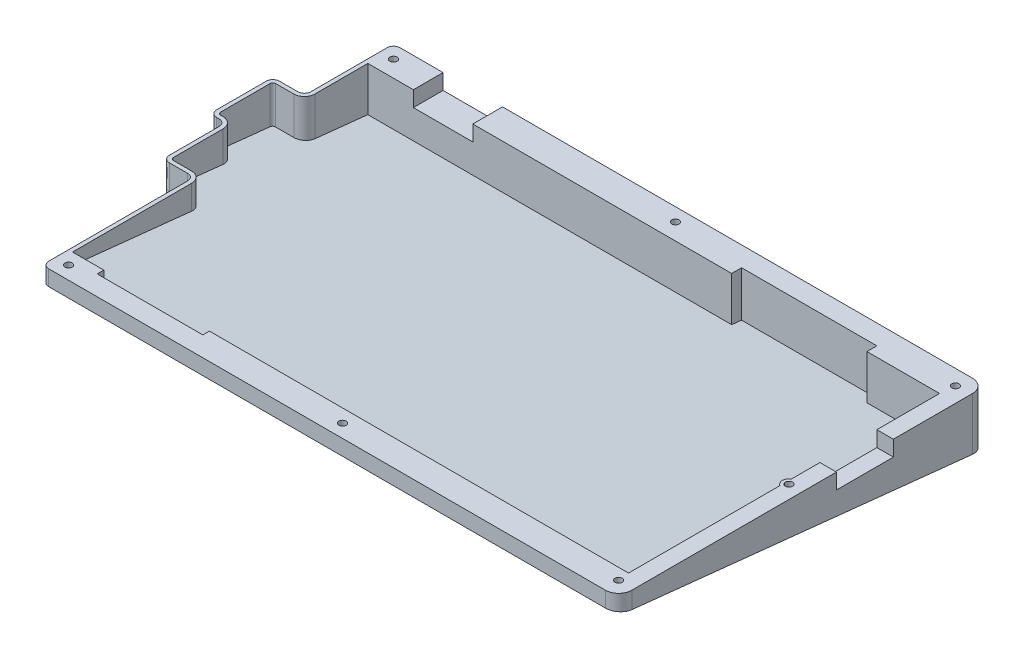
SolidWorks part; units mm, degrees
ref_plane "Front Plane" through (0, 0, 0) normal (0, 0, 1) x (1, 0, 0)
ref_plane "Top Plane" through (0, 0, 0) normal (0, 1, 0) x (1, 0, 0)
ref_plane "Right Plane" through (0, 0, 0) normal (1, 0, 0) x (0, 0, -1)
sketch "Sketch1" plane through (0, 0, 0) normal (0, 1, 0) x (1, 0, 0)
  line L0 (138.4196, 31.7518) -> (125.4196, 31.7518)
  line L1 (-35.0204, 31.7518) -> (107.4196, 31.7518)
  line L2 (140.4196, 29.7518) -> (140.4196, 6.7018)
  line L3 (-34.0204, 3.7518) -> (-34.0204, 22.7518)
  line L4 (136.4596, 27.7518) -> (136.4396, 27.7518)
  line L5 (142.4196, 4.7018) -> (147.9496, 4.7018)
  line L6 (-34.0204, 22.7518) -> (-12.0204, 22.7518)
  line L8 (149.9496, 2.7018) -> (149.9496, -12.3482)
  line L11 (147.9496, -14.3482) -> (147.1896, -14.3482)
  line L14 (145.1896, -16.3482) -> (145.1896, -31.3982)
  line L17 (143.1896, -33.3982) -> (137.6696, -33.3982)
  line L20 (135.6696, -35.3982) -> (135.6696, -77.4982)
  line L21 (-34.0204, -25.6003) -> (-34.0204, -71.4982)
  line L23 (133.6696, -79.4982) -> (-35.0204, -79.4982)
  line L28 (-39.0204, 27.7518) -> (-39.0204, 3.7518)
  line L31 (-34.0204, 3.7518) -> (-39.0204, 3.7518)
  line L32 (-34.0204, -13.4982) -> (-39.0204, -13.4982)
  line L33 (-39.0204, -75.4982) -> (-39.0204, -13.4982)
  line L34 (-34.0204, -71.4982) -> (92.9796, -71.4982)
  line L35 (92.9796, -71.4982) -> (92.9796, -73.4982)
  line L36 (92.9796, -73.4982) -> (124.9796, -73.4982)
  line L37 (124.9796, -73.4982) -> (124.9796, -71.4982)
  line L39 (134.4706, -35.3982) -> (134.4706, -71.4982)
  line L40 (134.4706, -71.4982) -> (124.9796, -71.4982)
  line L41 (137.6696, -32.1992) -> (143.1896, -32.1992)
  line L42 (-34.0204, -13.4982) -> (-34.0204, -22.1362)
  line L43 (143.9906, -31.3982) -> (143.9906, -16.3482)
  line L44 (-12.0204, 22.7518) -> (-12.0204, 25.7518)
  line L45 (147.1896, -13.1492) -> (147.9496, -13.1492)
  line L46 (148.7506, -12.3482) -> (148.7506, 2.7018)
  line L47 (-12.0204, 25.7518) -> (28.9796, 25.7518)
  line L48 (28.9796, 25.7518) -> (28.9796, 22.7518)
  line L49 (28.9796, 22.7518) -> (107.4196, 22.7518)
  line L50 (147.9496, 3.5027) -> (142.4196, 3.5027)
  line L51 (107.4196, 22.7518) -> (107.4196, 31.7518)
  line L52 (139.2206, 6.7018) -> (139.2206, 22.7518)
  line L53 (125.4196, 31.7518) -> (125.4196, 22.7518)
  line L54 (139.2206, 22.7518) -> (125.4196, 22.7518)
  arc A0 (138.4196, 31.7518) -> (140.4196, 29.7518) centre (138.4196, 29.7518) cw
  arc A1 (140.4196, 6.7018) -> (142.4196, 4.7018) centre (142.4196, 6.7018) ccw
  arc A2 (149.9496, 2.7018) -> (147.9496, 4.7018) centre (147.9496, 2.7018) ccw
  arc A3 (149.9496, -12.3482) -> (147.9496, -14.3482) centre (147.9496, -12.3482) cw
  arc A4 (147.1896, -14.3482) -> (145.1896, -16.3482) centre (147.1896, -16.3482) ccw
  arc A5 (145.1896, -31.3982) -> (143.1896, -33.3982) centre (143.1896, -31.3982) cw
  arc A6 (-35.0204, 31.7518) -> (-39.0204, 27.7518) centre (-35.0204, 27.7518) ccw
  arc A7 (-39.0204, -75.4982) -> (-35.0204, -79.4982) centre (-35.0204, -75.4982) ccw
  arc A8 (133.6696, -79.4982) -> (135.6696, -77.4982) centre (133.6696, -77.4982) ccw
  arc A9 (135.6696, -35.3982) -> (137.6696, -33.3982) centre (137.6696, -35.3982) cw
  circle A10 centre (-34.4204, 27.1518) radius 1.1
  circle A11 centre (51.0096, 27.7518) radius 1.1
  circle A12 centre (136.4396, 27.7518) radius 1.1
  circle A13 centre (-34.4204, -74.8982) radius 1.1
  circle A14 centre (48.6296, -75.4982) radius 1.1
  circle A15 centre (131.6496, -75.4982) radius 1.1
  circle A16 centre (-35.0204, -23.8682) radius 1.1
  arc A27 (-34.0204, -22.1362) -> (-34.0204, -25.6003) centre (-35.0204, -23.8682) cw
  arc A28 (139.2206, 6.7018) -> (142.4196, 3.5027) centre (142.4196, 6.7018) ccw
  arc A29 (147.9496, 3.5027) -> (148.7506, 2.7018) centre (147.9496, 2.7018) cw
  arc A30 (148.7506, -12.3482) -> (147.9496, -13.1492) centre (147.9496, -12.3482) cw
  arc A31 (147.1896, -13.1492) -> (143.9906, -16.3482) centre (147.1896, -16.3482) ccw
  arc A32 (143.9906, -31.3982) -> (143.1896, -32.1992) centre (143.1896, -31.3982) cw
  arc A33 (137.6696, -32.1992) -> (134.4706, -35.3982) centre (137.6696, -35.3982) ccw
extrude "Boss-Extrude2" add sketch "Sketch1" against normal blind 4.7 contours L41 A33 L39 L40 L37 L36 L35 L34 L21 A27 L42 L32 L33 A7 L23 A8 L20 A9 L17 A5 L14 A4 L11 A3 L8 A2 L5 A1 L2 A0 L0 L53 L54 L52 A28 L50 A29 L46 A30 L45 A31 L43 A32 A12 A13 A14 A15 | L1 A6 L28 L31 L3 L6 L44 L47 L48 L49 L51 A11 A10 region at (138.2833, 0, -29.6154) region at (31.7683, 0, -26.4895)
move or copy body "Body-Move/Copy1" bodies to move or copy 105 104 copy no rotation origin (55.4646, -2.35, 0) rotation axis (0, 0, 1) rotation angle 180
sketch "Sketch3" plane through (149.9496, 0, 0) normal (1, 0, 0) x (0, 0, -1)
  line L0 (-79.4982, 0) -> (-79.4982, -4.7) construction
  line L1 (-79.4982, 0) -> (-79.4982, -4.7)
  line L2 (31.7518, 0) -> (31.7518, -4.7) construction
  line L3 (31.7518, 0) -> (31.7518, -4.7)
  line L5 (-79.4982, -4.7) -> (31.7518, -16.3928)
  line L6 (31.7518, -16.3928) -> (31.7518, -4.7)
  line L7 (31.7518, -4.7) -> (-79.4982, -4.7)
  line M3 (-75.4982, -4.7) -> (-13.4982, -4.7)
  dimension "D1" = 6
extrude "Boss-Extrude3" add sketch "Sketch3" against normal up to surface (188.97 mm away) contours L6 L7 L5 M3 region at (149.9496, -8.5976, 5.3315) up to face at (-39.0204, -2.35, 4.8232)
sketch "Sketch4" plane through (0, -4.7, 0) normal (0, 1, 0) x (1, 0, 0)
  line L2 (145.9496, -79.4982) -> (149.9496, -79.4982)
  line L3 (149.9496, -79.4982) -> (149.9496, -75.4982)
  line L4 (-29.4904, 6.7018) -> (-29.4904, 29.7518)
  line L5 (-27.4904, 31.7518) -> (-39.0204, 31.7518)
  line L6 (-36.2604, -14.3482) -> (-37.0204, -14.3482)
  line L7 (-39.0204, -12.3482) -> (-39.0204, -79.4982)
  line L8 (-39.0204, -79.4982) -> (-22.7404, -79.4982)
  line L9 (-24.7404, -77.4982) -> (-24.7404, -35.3982)
  line L10 (-26.7404, -33.3982) -> (-32.2604, -33.3982)
  line L11 (-34.2604, -31.3982) -> (-34.2604, -16.3482)
  line L12 (-36.2604, -14.3482) -> (-37.0204, -14.3482)
  line L13 (-39.0204, -12.3482) -> (-39.0204, -79.4982)
  line L14 (-39.0204, -79.4982) -> (-22.7404, -79.4982)
  line L15 (-24.7404, -77.4982) -> (-24.7404, -35.3982)
  line L16 (-26.7404, -33.3982) -> (-32.2604, -33.3982)
  line L17 (-34.2604, -31.3982) -> (-34.2604, -16.3482)
  line L18 (-39.0204, 31.7518) -> (-39.0204, 2.7018)
  line L19 (-37.0204, 4.7018) -> (-31.4904, 4.7018)
  line L20 (-29.4904, 6.7018) -> (-29.4904, 29.7518)
  line L21 (-27.4904, 31.7518) -> (-39.0204, 31.7518)
  line L22 (-39.0204, 31.7518) -> (-39.0204, 2.7018)
  line L23 (-37.0204, 4.7018) -> (-31.4904, 4.7018)
  line L24 (145.9496, -79.4982) -> (149.9496, -79.4982)
  line L25 (149.9496, -79.4982) -> (149.9496, -75.4982)
  line L26 (149.9496, 31.7518) -> (145.9496, 31.7518)
  line L27 (149.9496, 27.7518) -> (149.9496, 31.7518)
  line L28 (149.9496, 31.7518) -> (145.9496, 31.7518)
  line L29 (149.9496, 27.7518) -> (149.9496, 31.7518)
  arc A1 (145.9496, -79.4982) -> (149.9496, -75.4982) centre (145.9496, -75.4982) ccw
  arc A2 (145.9496, -79.4982) -> (149.9496, -75.4982) centre (145.9496, -75.4982) ccw
  arc A3 (-27.4904, 31.7518) -> (-29.4904, 29.7518) centre (-27.4904, 29.7518) ccw
  arc A4 (-37.0204, 4.7018) -> (-39.0204, 2.7018) centre (-37.0204, 2.7018) ccw
  arc A5 (-39.0204, -12.3482) -> (-37.0204, -14.3482) centre (-37.0204, -12.3482) ccw
  arc A6 (-24.7404, -77.4982) -> (-22.7404, -79.4982) centre (-22.7404, -77.4982) ccw
  arc A7 (-24.7404, -35.3982) -> (-26.7404, -33.3982) centre (-26.7404, -35.3982) ccw
  arc A8 (-34.2604, -31.3982) -> (-32.2604, -33.3982) centre (-32.2604, -31.3982) ccw
  arc A9 (-34.2604, -16.3482) -> (-36.2604, -14.3482) centre (-36.2604, -16.3482) ccw
  arc A10 (-39.0204, -12.3482) -> (-37.0204, -14.3482) centre (-37.0204, -12.3482) ccw
  arc A11 (-24.7404, -77.4982) -> (-22.7404, -79.4982) centre (-22.7404, -77.4982) ccw
  arc A12 (-24.7404, -35.3982) -> (-26.7404, -33.3982) centre (-26.7404, -35.3982) ccw
  arc A13 (-34.2604, -31.3982) -> (-32.2604, -33.3982) centre (-32.2604, -31.3982) ccw
  arc A14 (-34.2604, -16.3482) -> (-36.2604, -14.3482) centre (-36.2604, -16.3482) ccw
  arc A15 (-31.4904, 4.7018) -> (-29.4904, 6.7018) centre (-31.4904, 6.7018) ccw
  arc A16 (-27.4904, 31.7518) -> (-29.4904, 29.7518) centre (-27.4904, 29.7518) ccw
  arc A17 (-37.0204, 4.7018) -> (-39.0204, 2.7018) centre (-37.0204, 2.7018) ccw
  arc A18 (-31.4904, 4.7018) -> (-29.4904, 6.7018) centre (-31.4904, 6.7018) ccw
  arc A19 (149.9496, 27.7518) -> (145.9496, 31.7518) centre (145.9496, 27.7518) ccw
  arc A20 (149.9496, 27.7518) -> (145.9496, 31.7518) centre (145.9496, 27.7518) ccw
  dimension "D1" = 0
  dimension "D2" = 0
  dimension "D3" = 0
  dimension "D4" = 0
extrude "Cut-Extrude1" cut sketch "Sketch4" against normal through all
ref_plane "Plane4" through (0, 15, 0) normal (0, 1, 0) x (1, 0, 0)
sketch "Sketch10" plane through (0, 15, 0) normal (0, 1, 0) x (1, 0, 0)
  line L0 (-14.4904, 22.7518) -> (3.5096, 22.7518)
  line L1 (144.9496, 3.7518) -> (144.9496, -13.4982)
  line L27 (-14.4904, 31.7518) -> (-14.4904, 22.7518)
  line L28 (-14.4904, 22.7518) -> (-28.2913, 22.7518)
  line L29 (-28.2913, 22.7518) -> (-28.2913, 6.7018)
  line L30 (-31.4904, 3.5027) -> (-37.0204, 3.5027)
  line L31 (-37.8213, 2.7018) -> (-37.8213, -12.3482)
  line L32 (-37.0204, -13.1492) -> (-36.2604, -13.1492)
  line L33 (-33.0613, -16.3482) -> (-33.0613, -31.3982)
  line L34 (-32.2604, -32.1992) -> (-26.7404, -32.1992)
  line L35 (-23.5413, -35.3982) -> (-23.5413, -71.4982)
  line L36 (-23.5413, -71.4982) -> (-14.0504, -71.4982)
  line L37 (-14.0504, -71.4982) -> (-14.0504, -73.4982)
  line L38 (-14.0504, -73.4982) -> (17.9496, -73.4982)
  line L39 (17.9496, -73.4982) -> (17.9496, -71.4982)
  line L40 (17.9496, -71.4982) -> (144.9496, -71.4982)
  line L41 (144.9496, -71.4982) -> (144.9496, -25.6003)
  line L42 (144.9496, -22.1362) -> (144.9496, -13.4982)
  line L43 (144.9496, -13.4982) -> (149.9496, -13.4982)
  line L44 (149.9496, -13.4982) -> (149.9496, 3.7518)
  line L45 (149.9496, 3.7518) -> (144.9496, 3.7518)
  line L46 (144.9496, 3.7518) -> (144.9496, 22.7518)
  line L47 (144.9496, 22.7518) -> (122.9496, 22.7518)
  line L48 (122.9496, 22.7518) -> (122.9496, 25.7518)
  line L49 (122.9496, 25.7518) -> (81.9496, 25.7518)
  line L50 (81.9496, 25.7518) -> (81.9496, 22.7518)
  line L51 (81.9496, 22.7518) -> (3.5096, 22.7518)
  line L52 (3.5096, 22.7518) -> (3.5096, 31.7518)
  line L53 (3.5096, 31.7518) -> (-14.4904, 31.7518)
  line L54 (-14.4904, 31.7518) -> (-14.4904, 22.7518)
  line L55 (-14.4904, 22.7518) -> (-28.2913, 22.7518)
  line L56 (-28.2913, 22.7518) -> (-28.2913, 6.7018)
  line L57 (-31.4904, 3.5027) -> (-37.0204, 3.5027)
  line L58 (-37.8213, 2.7018) -> (-37.8213, -12.3482)
  line L59 (-37.0204, -13.1492) -> (-36.2604, -13.1492)
  line L60 (-33.0613, -16.3482) -> (-33.0613, -31.3982)
  line L61 (-32.2604, -32.1992) -> (-26.7404, -32.1992)
  line L62 (-23.5413, -35.3982) -> (-23.5413, -71.4982)
  line L63 (-23.5413, -71.4982) -> (-14.0504, -71.4982)
  line L64 (-14.0504, -71.4982) -> (-14.0504, -73.4982)
  line L65 (-14.0504, -73.4982) -> (17.9496, -73.4982)
  line L66 (17.9496, -73.4982) -> (17.9496, -71.4982)
  line L67 (17.9496, -71.4982) -> (144.9496, -71.4982)
  line L68 (144.9496, -71.4982) -> (144.9496, -25.6003)
  line L69 (144.9496, -22.1362) -> (144.9496, -13.4982)
  line L70 (144.9496, -13.4982) -> (149.9496, -13.4982)
  line L71 (149.9496, -13.4982) -> (149.9496, 3.7518)
  line L72 (149.9496, 3.7518) -> (144.9496, 3.7518)
  line L73 (144.9496, 3.7518) -> (144.9496, 22.7518)
  line L74 (144.9496, 22.7518) -> (122.9496, 22.7518)
  line L75 (122.9496, 22.7518) -> (122.9496, 25.7518)
  line L76 (122.9496, 25.7518) -> (81.9496, 25.7518)
  line L77 (81.9496, 25.7518) -> (81.9496, 22.7518)
  line L78 (81.9496, 22.7518) -> (3.5096, 22.7518)
  line L79 (3.5096, 22.7518) -> (3.5096, 31.7518)
  line L80 (3.5096, 31.7518) -> (-14.4904, 31.7518)
  arc A7 (-31.4904, 3.5027) -> (-28.2913, 6.7018) centre (-31.4904, 6.7018) ccw
  arc A8 (-37.0204, 3.5027) -> (-37.8213, 2.7018) centre (-37.0204, 2.7018) ccw
  arc A9 (-37.8213, -12.3482) -> (-37.0204, -13.1492) centre (-37.0204, -12.3482) ccw
  arc A10 (-33.0613, -16.3482) -> (-36.2604, -13.1492) centre (-36.2604, -16.3482) ccw
  arc A11 (-33.0613, -31.3982) -> (-32.2604, -32.1992) centre (-32.2604, -31.3982) ccw
  arc A12 (-23.5413, -35.3982) -> (-26.7404, -32.1992) centre (-26.7404, -35.3982) ccw
  arc A13 (144.9496, -22.1362) -> (144.9496, -25.6003) centre (145.9496, -23.8682) ccw
  arc A14 (-31.4904, 3.5027) -> (-28.2913, 6.7018) centre (-31.4904, 6.7018) ccw
  arc A15 (-37.0204, 3.5027) -> (-37.8213, 2.7018) centre (-37.0204, 2.7018) ccw
  arc A16 (-37.8213, -12.3482) -> (-37.0204, -13.1492) centre (-37.0204, -12.3482) ccw
  arc A17 (-33.0613, -16.3482) -> (-36.2604, -13.1492) centre (-36.2604, -16.3482) ccw
  arc A18 (-33.0613, -31.3982) -> (-32.2604, -32.1992) centre (-32.2604, -31.3982) ccw
  arc A19 (-23.5413, -35.3982) -> (-26.7404, -32.1992) centre (-26.7404, -35.3982) ccw
  arc A20 (144.9496, -22.1362) -> (144.9496, -25.6003) centre (145.9496, -23.8682) ccw
  dimension "D1" = 0
extrude "Cut-Extrude2" cut sketch "Sketch10" against normal through all contours A20 L69 L1 L73 L74 L75 L76 L77 L78 L0 L55 L56 A14 L57 A15 L58 A16 L59 A17 L60 A18 L61 A19 L62 L63 L64 L65 L66 L67 L68 region at (57.9798, 15, 23.6888)
sketch "Sketch11" plane through (144.9496, 0, 0) normal (-1, 0, 0) x (0, 0, 1)
  line L0 (-22.7518, -15.4469) -> (71.4982, -5.5408)
  line L1 (71.4982, -5.5408) -> (71.4982, -3.5408)
  line L2 (71.4982, 0) -> (71.4982, -5.5408) construction
  line L3 (71.4982, -3.5408) -> (-22.7518, -13.4469)
  line L4 (-22.7518, 0) -> (-22.7518, -15.4469) construction
  line L5 (-22.7518, -13.4469) -> (-22.7518, -15.4469)
  dimension "D1" = 2
  dimension "D2" = 2
extrude "Boss-Extrude4" add sketch "Sketch11" along normal up to surface (182.7709 mm away)
sketch "Sketch12" plane through (0, -10.9348, 1.1493) normal (0, 0.9945, -0.1045) x (1, 0, 0)
  line L0 (-29.4904, 7.8943) -> (-29.4904, 24.0327) construction
  line L1 (-29.4904, 24.0327) -> (-37.8213, 24.0327) construction
  line L2 (-37.8213, 24.0327) -> (-37.8213, 5.715) construction
  line L3 (-37.0204, 5.8833) -> (-31.4904, 5.8833) construction
  line L4 (-36.2604, -13.2716) -> (-37.0204, -13.2716) construction
  line L5 (-37.8213, -13.1033) -> (-37.8213, -70.7364) construction
  line L6 (-37.8213, -70.7364) -> (-24.7404, -70.7364) construction
  line L7 (-24.7404, -70.7364) -> (-24.7404, -34.4376) construction
  line L8 (-26.7404, -32.4266) -> (-32.2604, -32.4266) construction
  line L9 (-34.2604, -30.4155) -> (-34.2604, -15.2826) construction
  line L10 (-29.4904, 7.8943) -> (-29.4904, 24.0327)
  line L11 (-29.4904, 24.0327) -> (-37.8213, 24.0327)
  line L12 (-37.8213, 24.0327) -> (-37.8213, 5.715)
  line L13 (-37.0204, 5.8833) -> (-31.4904, 5.8833)
  line L14 (-36.2604, -13.2716) -> (-37.0204, -13.2716)
  line L15 (-37.8213, -13.1033) -> (-37.8213, -70.7364)
  line L16 (-37.8213, -70.7364) -> (-24.7404, -70.7364)
  line L17 (-24.7404, -70.7364) -> (-24.7404, -34.4376)
  line L18 (-26.7404, -32.4266) -> (-32.2604, -32.4266)
  line L19 (-34.2604, -30.4155) -> (-34.2604, -15.2826)
  line L20 (-37.8213, 24.0327) -> (-37.8213, 25.9101)
  line L21 (-29.4904, 24.0327) -> (-29.4904, 27.1127)
  line L22 (-29.4904, 27.1127) -> (-37.8213, 25.9101)
  ellipse E0 centre (-31.4904, 7.8943) end of major axis (-31.4904, 9.9053) minor radius 2 (-31.4904, 5.8833) -> (-29.4904, 7.8943) ccw construction
  ellipse E1 centre (-37.0204, 3.8723) end of major axis (-37.0204, 5.8833) minor radius 2 (-37.0204, 5.8833) -> (-37.8213, 5.715) ccw construction
  ellipse E2 centre (-37.0204, -11.2606) end of major axis (-37.0204, -9.2496) minor radius 2 (-37.8213, -13.1033) -> (-37.0204, -13.2716) ccw construction
  ellipse E3 centre (-26.7404, -34.4376) end of major axis (-26.7404, -32.4266) minor radius 2 (-24.7404, -34.4376) -> (-26.7404, -32.4266) ccw construction
  ellipse E4 centre (-32.2604, -30.4155) end of major axis (-32.2604, -28.4045) minor radius 2 (-34.2604, -30.4155) -> (-32.2604, -32.4266) ccw construction
  ellipse E5 centre (-36.2604, -15.2826) end of major axis (-36.2604, -13.2716) minor radius 2 (-34.2604, -15.2826) -> (-36.2604, -13.2716) ccw construction
  ellipse E6 centre (-31.4904, 7.8943) end of major axis (-31.4904, 9.9053) minor radius 2 (-31.4904, 5.8833) -> (-29.4904, 7.8943) ccw
  ellipse E7 centre (-37.0204, 3.8723) end of major axis (-37.0204, 5.8833) minor radius 2 (-37.0204, 5.8833) -> (-37.8213, 5.715) ccw
  ellipse E8 centre (-37.0204, -11.2606) end of major axis (-37.0204, -9.2496) minor radius 2 (-37.8213, -13.1033) -> (-37.0204, -13.2716) ccw
  ellipse E9 centre (-26.7404, -34.4376) end of major axis (-26.7404, -32.4266) minor radius 2 (-24.7404, -34.4376) -> (-26.7404, -32.4266) ccw
  ellipse E10 centre (-32.2604, -30.4155) end of major axis (-32.2604, -28.4045) minor radius 2 (-34.2604, -30.4155) -> (-32.2604, -32.4266) ccw
  ellipse E11 centre (-36.2604, -15.2826) end of major axis (-36.2604, -13.2716) minor radius 2 (-34.2604, -15.2826) -> (-36.2604, -13.2716) ccw
sketch "Sketch26" plane through (-37.8213, 0, 0) normal (-1, 0, 0) x (0, 0, 1)
  line L0 (14.1808, -9.5651) -> (-4.5344, -11.5322)
  line L1 (-4.5344, -13.5322) -> (14.1808, -11.5651)
  line L4 (-22.7518, -15.4469) -> (-4.5344, -13.5322)
  line L5 (-4.5344, -13.5322) -> (-4.5344, -11.5322)
  line L6 (-4.5344, -11.5322) -> (-22.7518, -13.4469)
  line L7 (-22.7518, -13.4469) -> (-22.7518, -15.4469)
  line L8 (-22.7518, -15.4469) -> (-4.5344, -13.5322)
  line L9 (-4.5344, -13.5322) -> (-4.5344, -11.5322)
  line L10 (-4.5344, -11.5322) -> (-22.7518, -13.4469)
  line L11 (-22.7518, -13.4469) -> (-22.7518, -15.4469)
  line L12 (14.1808, -9.5651) -> (14.1808, -11.5651)
  line L13 (14.1808, -11.5651) -> (71.4982, -5.5408)
  line L14 (71.4982, -5.5408) -> (71.4982, -3.5408)
  line L15 (71.4982, -3.5408) -> (14.1808, -9.5651)
  line L16 (14.1808, -9.5651) -> (14.1808, -11.5651)
  line L17 (14.1808, -11.5651) -> (71.4982, -5.5408)
  line L18 (71.4982, -5.5408) -> (71.4982, -3.5408)
  line L19 (71.4982, -3.5408) -> (14.1808, -9.5651)
  line M9 (14.1808, -9.5651) -> (14.1808, -11.5651)
  line M10 (14.1808, -11.5651) -> (71.4982, -5.5408)
  line M11 (71.4982, -5.5408) -> (71.4982, -3.5408)
  line M12 (71.4982, -3.5408) -> (14.1808, -9.5651)
  dimension "D1" = 0
  dimension "D2" = 0
extrude "Boss-Extrude10" add sketch "Sketch26" along normal blind 11 contours L10 L11 L8 L9 | L9 L1 L0 M9 | M12 M9 M10 M11 region at (-37.8213, -11.5487, 4.8232) region at (-37.8213, -7.553, 42.8395) region at (-37.8213, -13.4895, -13.6431)
sketch "Sketch28" plane through (0, -10.9348, 1.1493) normal (0, 0.9945, -0.1045) x (1, 0, 0)
  line L0 (-48.8213, 24.0327) -> (-52.7132, 28.3929)
  line L1 (-52.7132, 28.3929) -> (-29.4904, 30.8021)
  line L2 (-29.4904, 30.8021) -> (-29.4904, 24.0327)
  line L10 (-29.4904, 7.8943) -> (-29.4904, 24.0327)
  line L11 (-29.4904, 24.0327) -> (-48.8213, 24.0327)
  line L12 (-48.8213, 24.0327) -> (-48.8213, -70.7364)
  line L13 (-48.8213, -70.7364) -> (-24.7404, -70.7364)
  line L14 (-24.7404, -70.7364) -> (-24.7404, -34.4376)
  line L15 (-26.7404, -32.4266) -> (-32.2604, -32.4266)
  line L16 (-34.2604, -30.4155) -> (-34.2604, -15.2826)
  line L17 (-36.2604, -13.2716) -> (-37.0204, -13.2716)
  line L18 (-39.0204, -11.2606) -> (-39.0204, 3.8723)
  line L19 (-37.0204, 5.8833) -> (-31.4904, 5.8833)
  line L20 (-29.4904, 7.8943) -> (-29.4904, 24.0327)
  line L21 (-29.4904, 24.0327) -> (-48.8213, 24.0327)
  line L22 (-48.8213, 24.0327) -> (-48.8213, -70.7364)
  line L23 (-48.8213, -70.7364) -> (-24.7404, -70.7364)
  line L24 (-24.7404, -70.7364) -> (-24.7404, -34.4376)
  line L25 (-26.7404, -32.4266) -> (-32.2604, -32.4266)
  line L26 (-34.2604, -30.4155) -> (-34.2604, -15.2826)
  line L27 (-36.2604, -13.2716) -> (-37.0204, -13.2716)
  line L28 (-39.0204, -11.2606) -> (-39.0204, 3.8723)
  line L29 (-37.0204, 5.8833) -> (-31.4904, 5.8833)
  ellipse E6 centre (-31.4904, 7.8943) end of major axis (-31.4904, 9.9053) minor radius 2 (-31.4904, 5.8833) -> (-29.4904, 7.8943) ccw
  ellipse E7 centre (-26.7404, -34.4376) end of major axis (-26.7404, -32.4266) minor radius 2 (-24.7404, -34.4376) -> (-26.7404, -32.4266) ccw
  ellipse E8 centre (-32.2604, -30.4155) end of major axis (-32.2604, -28.4045) minor radius 2 (-34.2604, -30.4155) -> (-32.2604, -32.4266) ccw
  ellipse E9 centre (-36.2604, -15.2826) end of major axis (-36.2604, -13.2716) minor radius 2 (-34.2604, -15.2826) -> (-36.2604, -13.2716) ccw
  ellipse E10 centre (-37.0204, -11.2606) end of major axis (-37.0204, -9.2496) minor radius 2 (-39.0204, -11.2606) -> (-37.0204, -13.2716) ccw
  ellipse E11 centre (-37.0204, 3.8723) end of major axis (-37.0204, 5.8833) minor radius 2 (-37.0204, 5.8833) -> (-39.0204, 3.8723) ccw
  ellipse E12 centre (-31.4904, 7.8943) end of major axis (-31.4904, 9.9053) minor radius 2 (-31.4904, 5.8833) -> (-29.4904, 7.8943) ccw
  ellipse E13 centre (-26.7404, -34.4376) end of major axis (-26.7404, -32.4266) minor radius 2 (-24.7404, -34.4376) -> (-26.7404, -32.4266) ccw
  ellipse E14 centre (-32.2604, -30.4155) end of major axis (-32.2604, -28.4045) minor radius 2 (-34.2604, -30.4155) -> (-32.2604, -32.4266) ccw
  ellipse E15 centre (-36.2604, -15.2826) end of major axis (-36.2604, -13.2716) minor radius 2 (-34.2604, -15.2826) -> (-36.2604, -13.2716) ccw
  ellipse E16 centre (-37.0204, -11.2606) end of major axis (-37.0204, -9.2496) minor radius 2 (-39.0204, -11.2606) -> (-37.0204, -13.2716) ccw
  ellipse E17 centre (-37.0204, 3.8723) end of major axis (-37.0204, 5.8833) minor radius 2 (-37.0204, 5.8833) -> (-39.0204, 3.8723) ccw
  ellipse M17 centre (-31.4904, 7.8943) end of major axis (-31.4904, 9.9053) minor radius 2 (-31.4904, 5.8833) -> (-29.4904, 7.8943) ccw
  line M18 (-29.4904, 7.8943) -> (-29.4904, 24.0327)
  line M19 (-29.4904, 24.0327) -> (-48.8213, 24.0327)
  line M20 (-48.8213, 24.0327) -> (-48.8213, -70.7364)
  line M21 (-48.8213, -70.7364) -> (-24.7404, -70.7364)
  line M22 (-24.7404, -70.7364) -> (-24.7404, -34.4376)
  ellipse M23 centre (-26.7404, -34.4376) end of major axis (-26.7404, -32.4266) minor radius 2 (-24.7404, -34.4376) -> (-26.7404, -32.4266) ccw
  line M24 (-26.7404, -32.4266) -> (-32.2604, -32.4266)
  ellipse M25 centre (-32.2604, -30.4155) end of major axis (-32.2604, -28.4045) minor radius 2 (-32.2604, -32.4266) -> (-34.2604, -30.4155) cw
  line M26 (-34.2604, -30.4155) -> (-34.2604, -15.2826)
  ellipse M27 centre (-36.2604, -15.2826) end of major axis (-36.2604, -13.2716) minor radius 2 (-34.2604, -15.2826) -> (-36.2604, -13.2716) ccw
  line M28 (-36.2604, -13.2716) -> (-37.0204, -13.2716)
  ellipse M29 centre (-37.0204, -11.2606) end of major axis (-37.0204, -9.2496) minor radius 2 (-37.0204, -13.2716) -> (-39.0204, -11.2606) cw
  line M30 (-39.0204, -11.2606) -> (-39.0204, 3.8723)
  ellipse M31 centre (-37.0204, 3.8723) end of major axis (-37.0204, 5.8833) minor radius 2 (-39.0204, 3.8723) -> (-37.0204, 5.8833) cw
  line M32 (-37.0204, 5.8833) -> (-31.4904, 5.8833)
  dimension "D1" = 0
extrude "Cut-Extrude8" cut sketch "Sketch28" against normal blind 11 contours M32 M17 M18 M19 M20 M21 M22 M23 M24 M25 M26 M27 M28 M29 M30 M31 | L2 L1 L0 M19 region at (-39.4803, -13.7524, -25.6581) region at (-38.8035, -7.967, 29.3861)
sketch "Sketch30" plane through (122.9496, 0, 0) normal (-1, 0, 0) x (0, 0, 1)
  line L0 (-25.7518, -15.7622) -> (-22.7518, -15.4469)
  line L1 (-22.7518, -15.4469) -> (-22.7518, -13.4469)
  line L2 (-22.7518, -15.4469) -> (-22.7518, -13.4469) construction
  line L3 (-22.7518, -13.4469) -> (-25.7518, -13.7622)
  line L4 (-25.7518, 0) -> (-25.7518, -15.7622) construction
  line L5 (-25.7518, -13.7622) -> (-25.7518, -15.7622)
extrude "Boss-Extrude11" add sketch "Sketch30" along normal up to surface (41 mm away)
sketch "Sketch32" plane through (17.9496, 0, 0) normal (-1, 0, 0) x (0, 0, 1)
  line L0 (73.4982, -5.3306) -> (71.4982, -5.5408)
  line L1 (71.4982, -5.5408) -> (71.4982, -3.5408)
  line L2 (71.4982, -3.5408) -> (73.4982, -3.3306)
  line L3 (73.4982, 0) -> (73.4982, -5.3306) construction
  line L4 (73.4982, -3.3306) -> (73.4982, -5.3306)
  dimension "D1" = 2
extrude "Boss-Extrude14" add sketch "Sketch32" along normal up to surface (32 mm away)
